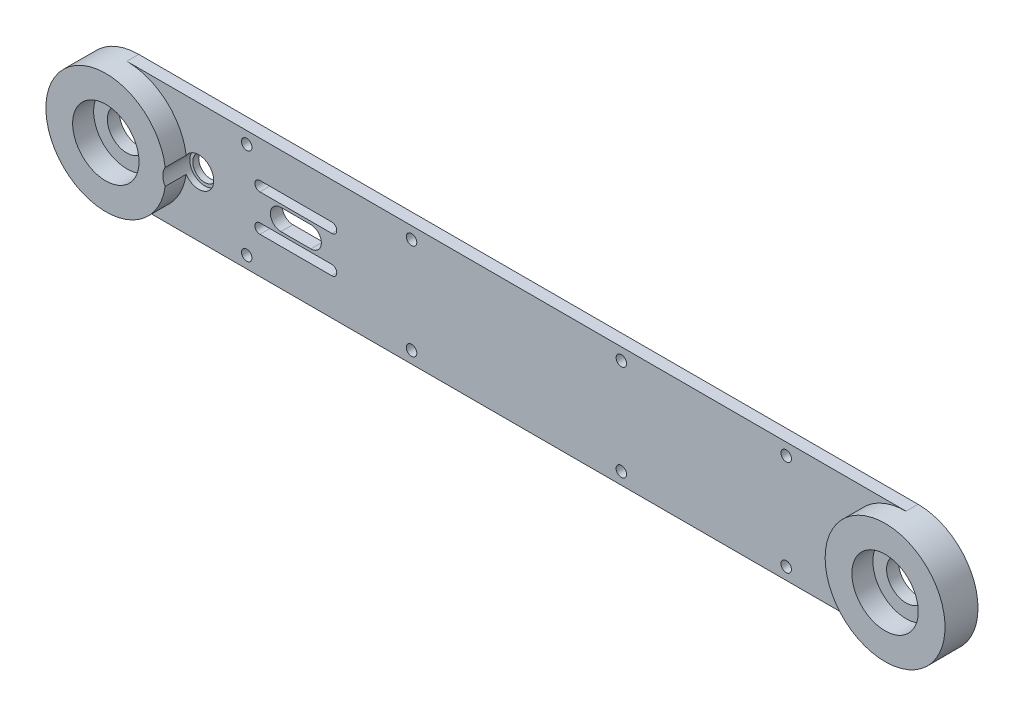
SolidWorks part; units mm, degrees
ref_plane "Ebene vorne" through (0, 0, 0) normal (0, 0, 1) x (1, 0, 0)
ref_plane "Ebene oben" through (0, 0, 0) normal (0, 1, 0) x (1, 0, 0)
ref_plane "Ebene rechts" through (0, 0, 0) normal (1, 0, 0) x (0, 0, -1)
sketch "Skizze1" plane through (0, 0, 0) normal (0, 0, 1) x (1, 0, 0)
  line L0 (-130, 0) -> (0, 0) construction
  line L1 (-130, -20) -> (130, -20)
  line L2 (-130, -20) -> (-130, 20) construction
  line L3 (-130, 20) -> (130, 20)
  line L4 (130, -20) -> (130, 20) construction
  line L5 (-130, -20) -> (130, 20) construction
  line L6 (-130, 20) -> (130, -20) construction
  line L7 (0, 0) -> (130, 0) construction
  arc A0 (-130, 20) -> (-130, -20) centre (-130, 0) ccw
  arc A1 (130, 20) -> (130, -20) centre (130, 0) cw
  point P0 (0, 0)
  dimension "D1" = 260
  dimension "D2" = 40
extrude "Aufsatz-Linear austragen1" add sketch "Skizze1" along normal blind 4
sketch "Skizze2" plane through (0, 0, 4) normal (0, 0, 1) x (1, 0, 0)
  circle A0 centre (-130, 0) radius 20
  circle A1 centre (-130, 0) radius 11.075
  dimension "D1" = 22.15
extrude "Aufsatz-Linear austragen2" add sketch "Skizze2" along normal blind 7
sketch "Skizze3" plane through (0, 0, 4) normal (0, 0, 1) x (1, 0, 0)
  circle A0 centre (-130, 0) radius 6.5
  dimension "D1" = 13
extrude "Schnitt-Linear austragen1" cut sketch "Skizze3" against normal through all and the other way through all
mirror "Spiegeln1" about plane through (0, 0, 0) normal (1, 0, 0) of "Aufsatz-Linear austragen2", "Schnitt-Linear austragen1"
sketch "Skizze4" plane through (0, 0, 4) normal (0, 0, 1) x (1, 0, 0)
  line L0 (-130, 20) -> (130, 20) construction
  line L1 (0, 0) -> (-130, 0) construction
  line L2 (0, 0) -> (0, 20) construction
  line L3 (-90, 12) -> (-35, 12) construction
  line L4 (-90, 14.25) -> (-35, 14.25) construction
  circle A0 centre (-130, 0) radius 30 construction
  circle A1 centre (-90, 16) radius 4 construction
  circle A2 centre (-90, 16) radius 1.75
  circle A3 centre (-90, -16) radius 4 construction
  circle A4 centre (-90, -16) radius 1.75
  circle A5 centre (90, -16) radius 4 construction
  circle A6 centre (90, 16) radius 4 construction
  circle A7 centre (90, -16) radius 1.75
  circle A8 centre (90, 16) radius 1.75
  circle A9 centre (-35, 16) radius 4 construction
  circle A10 centre (-35, 16) radius 1.75
  circle A11 centre (-35, -16) radius 4 construction
  circle A12 centre (-35, -16) radius 1.75
  circle A13 centre (35, -16) radius 4 construction
  circle A14 centre (35, 16) radius 4 construction
  circle A15 centre (35, -16) radius 1.75
  circle A16 centre (35, 16) radius 1.75
  dimension "D1" = 60
  dimension "D2" = 8
  dimension "D3" = 3.5
  dimension "D4" = 40
  dimension "D5" = 55
extrude "Schnitt-Linear austragen2" cut sketch "Skizze4" against normal through all
sketch "Skizze5" plane through (0, 0, 0) normal (0, 0, -1) x (-1, 0, 0)
  line L0 (130, 0) -> (106, 0) construction
  circle A0 centre (106, 0) radius 4
  dimension "D1" = 8
  dimension "D2" = 24
extrude "Schnitt-Linear austragen3" cut sketch "Skizze5" against normal through all
sketch "Skizze6" plane through (0, 0, 4) normal (0, 0, 1) x (1, 0, 0)
  circle A0 centre (-106, 0) radius 5
  dimension "D1" = 10
extrude "Schnitt-Linear austragen4" cut sketch "Skizze6" against normal blind 2 and the other way through all
sketch "Skizze7" plane through (0, 0, 0) normal (0, 0, -1) x (-1, 0, 0)
  line L0 (0, 0) -> (106, 0) construction
  line L1 (68.6, 0) -> (78.6, 0) construction
  line L2 (68.6, 3.5) -> (78.6, 3.5)
  line L3 (68.6, -3.5) -> (78.6, -3.5)
  line L4 (61.6, 6.12) -> (85.6, 6.12) construction
  line L5 (61.6, 7.77) -> (85.6, 7.77)
  line L6 (61.6, 4.47) -> (85.6, 4.47)
  line L7 (61.6, -6.12) -> (85.6, -6.12) construction
  line L8 (61.6, -7.77) -> (85.6, -7.77)
  line L9 (61.6, -4.47) -> (85.6, -4.47)
  arc A0 (68.6, 3.5) -> (68.6, -3.5) centre (68.6, 0) ccw
  arc A1 (78.6, -3.5) -> (78.6, 3.5) centre (78.6, 0) ccw
  arc A2 (61.6, 7.77) -> (61.6, 4.47) centre (61.6, 6.12) ccw
  arc A3 (85.6, 4.47) -> (85.6, 7.77) centre (85.6, 6.12) ccw
  arc A4 (61.6, -7.77) -> (61.6, -4.47) centre (61.6, -6.12) cw
  arc A5 (85.6, -4.47) -> (85.6, -7.77) centre (85.6, -6.12) cw
  point P6 (73.6, 0)
  point P13 (73.6, 6.12)
  point P20 (73.6, -6.12)
  dimension "D1" = 7
  dimension "D2" = 3.3
  dimension "D3" = 7
  dimension "D4" = 7
  dimension "D5" = 6.12
  dimension "D6" = 24
  dimension "D7" = 32.4
extrude "Schnitt-Linear austragen5" cut sketch "Skizze7" against normal through all
